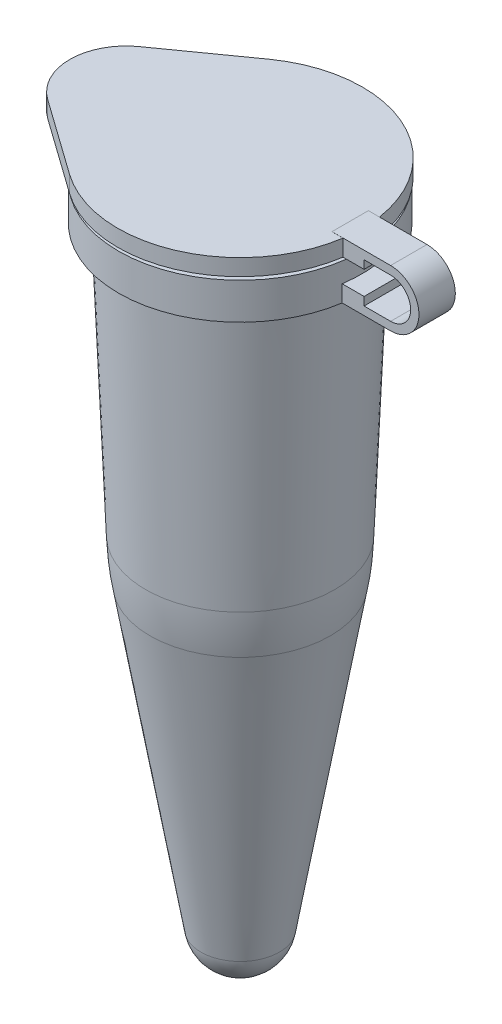
SolidWorks part; units mm, degrees
ref_plane "Front Plane" through (0, 0, 0) normal (0, 0, 1) x (1, 0, 0)
ref_plane "Top Plane" through (0, 0, 0) normal (0, 1, 0) x (1, 0, 0)
ref_plane "Right Plane" through (0, 0, 0) normal (1, 0, 0) x (0, 0, -1)
sketch "Sketch1" plane through (0, 0, 0) normal (0, 1, 0) x (1, 0, 0)
  circle A0 centre (0, 0) radius 3.7338
  circle A1 centre (0, 0) radius 2.6797
  dimension "D1" = 7.4676
  dimension "D2" = 5.3594
extrude "Boss-Extrude1" add sketch "Sketch1" against normal blind 1.1176
sketch "Sketch2" plane through (0, 0, 0) normal (0, 0, 1) x (1, 0, 0)
  line L0 (0, -1.1176) -> (0, -20.9296)
  line L1 (-3.2385, -1.1176) -> (-2.9065, -9.4171)
  line L2 (-3.7338, -1.1176) -> (3.7338, -1.1176) construction
  line L3 (-2.7708, -10.7148) -> (-1.2065, -19.911)
  line L4 (-3.2385, -1.1176) -> (0, -1.1176)
  arc A0 (-1.2065, -19.911) -> (0, -20.9296) centre (0, -19.7058) ccw
  arc A1 (-2.9065, -9.4171) -> (-2.7708, -10.7148) centre (7.2454, -9.0111) ccw
  arc A4 (0, -20.909) -> (1.2062, -19.8923) centre (0, -19.6852) ccw construction
  point P7 (-2.9591, -8.1026)
  point P10 (-2.8479, -10.2616)
  dimension "D5" = 10.16
  dimension "D1" = 3.2385
  dimension "D2" = 6.985
  dimension "D3" = 2.9591
  dimension "D4" = 9.144
  dimension "D8" = 19.812
revolve "Revolve1" add sketch "Sketch2" angle 360 about L0
shell "Shell1" thickness 0.5715 removed face at (-3.2385, -1.1176, 0)
combine bodies "Combine1" operation type add bodies to combine 101 102
sketch "Sketch3" plane through (0, 0, 0) normal (0, 0, 1) x (1, 0, 0)
  line L0 (3.7338, -1.1176) -> (4.3653, -1.1176)
  line L1 (4.3653, -0.8625) -> (4.3653, -0.6074)
  line L2 (4.3653, -0.6074) -> (3.3793, -0.6074)
  line L3 (3.3793, -0.6074) -> (3.3793, -1.1176)
  line L4 (-3.7338, -1.1176) -> (3.7338, -1.1176) construction
  line L5 (3.3793, -1.1176) -> (3.7338, -1.1176)
  line L6 (4.3653, -1.1176) -> (5.18, -1.1176)
  line L8 (5.18, -0.8625) -> (4.3653, -0.8625)
  line L9 (3.3793, 0.1127) -> (4.3653, 0.1127)
  line L10 (4.3653, 0.1127) -> (4.3653, 0.3677)
  line L11 (4.3653, 0.6228) -> (3.3793, 0.6228)
  line L12 (3.3793, 0.6228) -> (3.3793, 0.1127)
  line L13 (4.3653, 0.6228) -> (5.18, 0.6228)
  line L15 (5.18, 0.3677) -> (4.3653, 0.3677)
  arc A0 (5.18, 0.6228) -> (5.18, -1.1176) centre (5.18, -0.2474) cw
  arc A1 (5.18, 0.3677) -> (5.18, -0.8625) centre (5.18, -0.2474) cw
extrude "Boss-Extrude2" add sketch "Sketch3" along normal mid plane 1.1176
sketch "Sketch4" plane through (0, 0.1127, 0) normal (0, -1, 0) x (1, 0, 0)
  circle A0 centre (0, 0) radius 2.615
  circle A1 centre (0, 0) radius 2.107
  dimension "D1" = 0.508
extrude "Boss-Extrude3" add sketch "Sketch4" along normal blind 1.1176 separate body
sketch "Sketch6" plane through (0, 0.1127, 0) normal (0, -1, 0) x (1, 0, 0)
  line L0 (-2.1799, -3.0626) -> (-4.5074, -1.4059)
  line L1 (0, 0) -> (1.7312, 0) construction
  line L2 (-2.1799, 3.0626) -> (-4.5074, 1.4059)
  arc A0 (-2.1799, -3.0626) -> (-2.1799, 3.0626) centre (0, 0) ccw
  arc A1 (-4.5074, 1.4059) -> (-4.5074, -1.4059) centre (-3.5067, 0) ccw
  point P5 (3.7592, 0)
  point P6 (-5.2324, 0)
  dimension "D1" = 7.5184
  dimension "D2" = 8.9916
extrude "Boss-Extrude4" add sketch "Sketch6" against normal blind 0.508
ref_plane "SamplingPlane" through (0, -14.3793, 0) normal (0, 1, 0) x (1, 0, 0)
ref_point "SamplingPoint"
